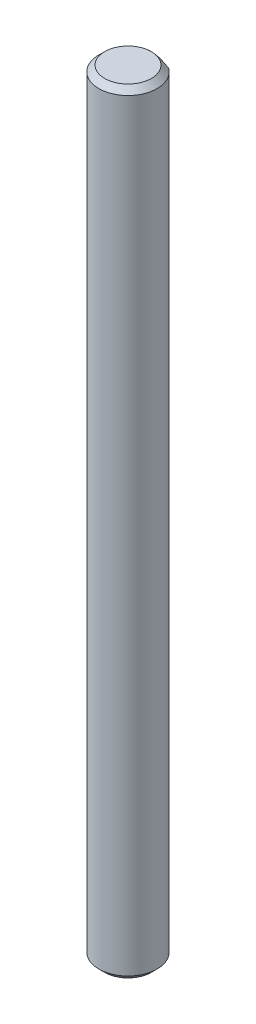
SolidWorks part; units mm, degrees
ref_plane "Front Plane" through (0, 0, 0) normal (0, 0, 1) x (1, 0, 0)
ref_plane "Top Plane" through (0, 0, 0) normal (0, 1, 0) x (1, 0, 0)
ref_plane "Right Plane" through (0, 0, 0) normal (1, 0, 0) x (0, 0, -1)
sketch "Sketch3" plane through (0, 0, 0) normal (1, 0, 0) x (0, 0, -1)
  line L0 (0, 33.2) -> (0, -33.2)
  line L1 (0, 33.2) -> (2.5, 33.2)
  line L2 (2.5, 33.2) -> (2.5, -33.2)
  line L3 (2.5, -33.2) -> (0, -33.2)
  point P4 (0, 0)
  dimension "D1" = 66.4
  dimension "D2" = 2.5
revolve "Revolve2" add sketch "Sketch3" angle 360 about L0
sketch "Esboço1" plane through (0, 33.2, 0) normal (0, 1, 0) x (1, 0, 0)
  line L0 (-1.5, 2) -> (1.5, 2)
  line L1 (0, 2) -> (0, -2.5) construction
  circle A2 centre (0, 0) radius 2.5 construction
  arc A3 (1.5, 2) -> (-1.5, 2) centre (0, 0) ccw
  dimension "D1" = 4.5
extrude "Corte-extrusão1" cut sketch "Esboço1" against normal blind 22
chamfer "Chanfro1" distance 0.5 angle 45 2 edges at (0, -33.2, 2.5) (0, 33.2, 2.5)
